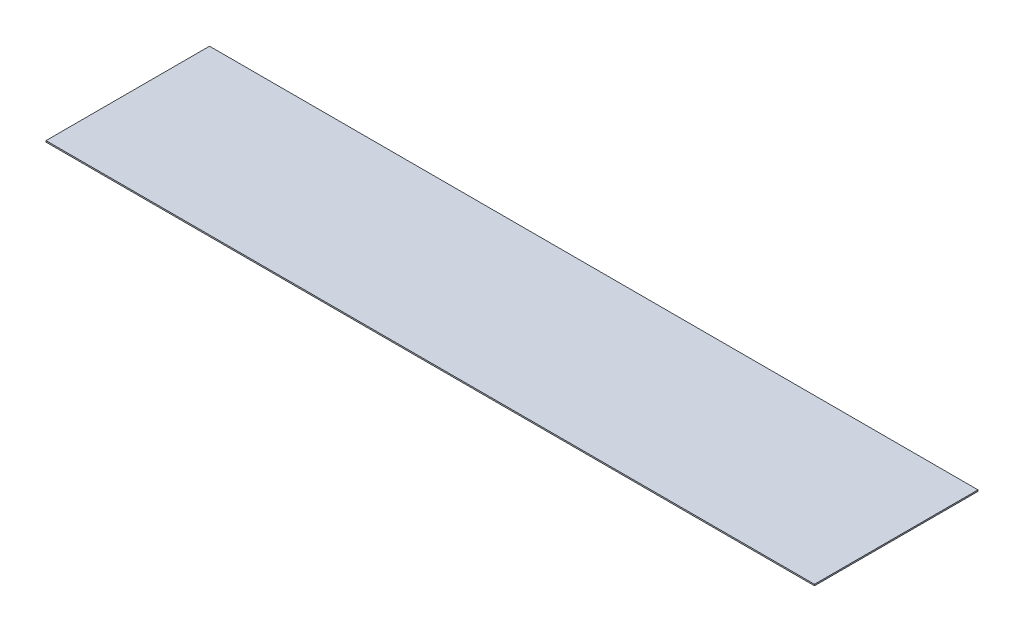
SolidWorks part; units mm, degrees
material "Natural Rubber"
ref_plane "Front" through (0, 0, 0) normal (0, 0, 1) x (1, 0, 0)
ref_plane "Top" through (0, 0, 0) normal (0, 1, 0) x (1, 0, 0)
ref_plane "Right" through (0, 0, 0) normal (1, 0, 0) x (0, 0, -1)
sketch "Sketch1" plane through (0, 0, 0) normal (0, 1, 0) x (1, 0, 0)
  line L1 (-1447.8, 825.5) -> (1447.8, 825.5)
  line L2 (-1447.8, 825.5) -> (-1447.8, -825.5)
  line L3 (-1447.8, -825.5) -> (1447.8, -825.5)
  line L4 (1447.8, 825.5) -> (1447.8, -825.5)
  line L5 (-1447.8, 825.5) -> (1447.8, -825.5) construction
  line L6 (-1447.8, -825.5) -> (1447.8, 825.5) construction
  point P0 (0, 0)
  dimension "D1" = 2895.6
  dimension "D2" = 1651
extrude "Boss-Extrude1" [suppressed] add sketch "Sketch1" along normal blind 1473.2
sketch "Sketch2" [suppressed] plane through (0, 0, 0) normal (0, -1, 0) x (1, 0, 0)
  line L0 (0, 0) -> (2162.175, 0) construction
  line L1 (1447.8, 825.5) -> (1447.8, -825.5) construction
  line L2 (1752.6, 663.575) -> (2571.75, 663.575)
  line L3 (1752.6, 663.575) -> (1752.6, -663.575)
  line L4 (1752.6, -663.575) -> (2571.75, -663.575)
  line L5 (2571.75, 663.575) -> (2571.75, -663.575)
  line L6 (1752.6, 663.575) -> (2571.75, -663.575) construction
  line L7 (1752.6, -663.575) -> (2571.75, 663.575) construction
  dimension "D1" = 1327.15
  dimension "D2" = 819.15
  dimension "D3" = 304.8
extrude "Boss-Extrude2" [suppressed] add sketch "Sketch2" against normal blind 736.6 separate body
sketch "Sketch3" plane through (0, 0, 0) normal (0, 1, 0) x (-1, 0, 0)
  line L2 (6553.2, 914.4) -> (-6553.2, 914.4)
  line L3 (6553.2, 914.4) -> (6553.2, -914.4)
  line L4 (6553.2, -914.4) -> (-6553.2, -914.4)
  line L5 (-6553.2, 914.4) -> (-6553.2, -914.4)
  line L6 (6553.2, 914.4) -> (-6553.2, -914.4) construction
  line L7 (6553.2, -914.4) -> (-6553.2, 914.4) construction
  dimension "D1" = 1828.8
  dimension "D2" = 13106.4
extrude "Boss-Extrude3" add sketch "Sketch3" along normal blind 304.8 separate body
sketch "Sketch4" plane through (0, 304.8, 0) normal (0, 1, 0) x (1, 0, 0)
  line L0 (6553.2, -914.4) -> (6553.2, 914.4) construction
  line L1 (-7162.8, 1524) -> (7162.8, 1524)
  line L2 (-7162.8, 1524) -> (-7162.8, -1524)
  line L3 (-7162.8, -1524) -> (7162.8, -1524)
  line L4 (7162.8, 1524) -> (7162.8, -1524)
  line L5 (-7162.8, 1524) -> (7162.8, -1524) construction
  line L6 (-7162.8, -1524) -> (7162.8, 1524) construction
  line L7 (-6553.2, -914.4) -> (6553.2, -914.4) construction
  point P0 (0, 0)
  dimension "D1" = 609.6
  dimension "D2" = 609.6
extrude "Boss-Extrude4" add sketch "Sketch4" along normal blind 25.4 separate body
